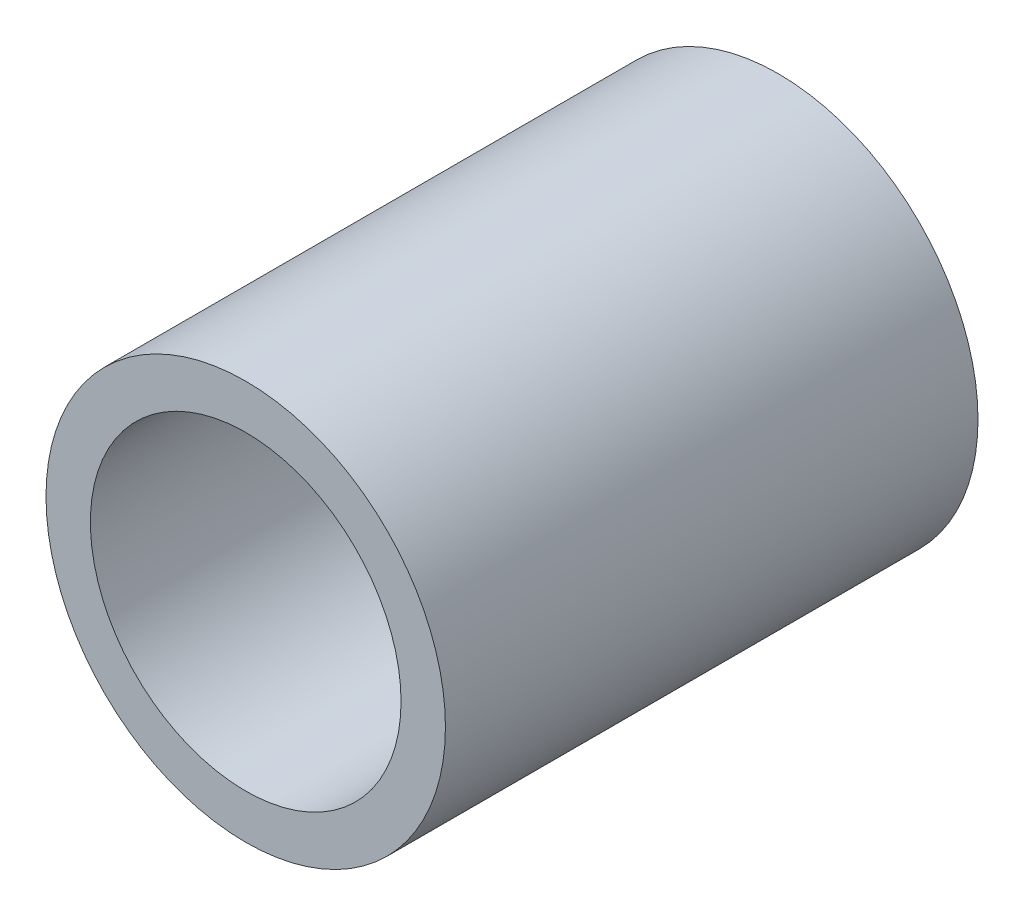
SolidWorks part; units mm, degrees
material "3003 Alloy"
ref_plane "Front Plane" through (0, 0, 0) normal (0, 0, 1) x (1, 0, 0)
ref_plane "Top Plane" through (0, 0, 0) normal (0, 1, 0) x (1, 0, 0)
ref_plane "Right Plane" through (0, 0, 0) normal (1, 0, 0) x (0, 0, -1)
sketch "Sketch1" plane through (0, 0, 0) normal (0, 0, 1) x (1, 0, 0)
  circle A0 centre (0, 0) radius 3.5
  dimension "D1" = 7
extrude "Extrude1" add sketch "Sketch1" along normal blind 12
shell "Shell1" thickness 1 removed face at (3.5, 0, 0) removed face at (3.5, 0, 12) outward yes
